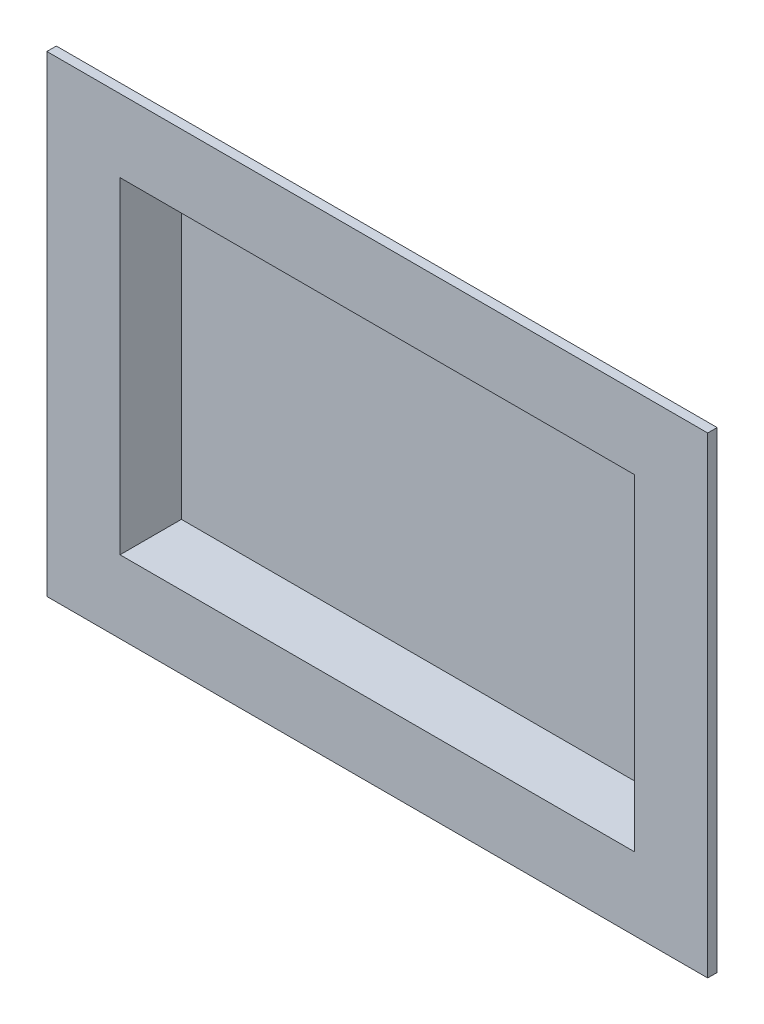
SolidWorks part; units mm, degrees
material "6063-O"
ref_plane "Front Plane" through (0, 0, 0) normal (0, 0, 1) x (1, 0, 0)
ref_plane "Top Plane" through (0, 0, 0) normal (0, 1, 0) x (1, 0, 0)
ref_plane "Right Plane" through (0, 0, 0) normal (1, 0, 0) x (0, 0, -1)
sketch "Sketch1" plane through (0, 0, 0) normal (0, 0, 1) x (1, 0, 0)
  line L1 (-71.755, -46.482) -> (71.755, -46.482)
  line L2 (-71.755, -46.482) -> (-71.755, 46.482)
  line L3 (-71.755, 46.482) -> (71.755, 46.482)
  line L4 (71.755, -46.482) -> (71.755, 46.482)
  line L5 (-71.755, -46.482) -> (71.755, 46.482) construction
  line L6 (-71.755, 46.482) -> (71.755, -46.482) construction
  point P0 (0, 0)
  dimension "D1" = 143.51
  dimension "D2" = 92.964
extrude "Boss-Extrude1" add sketch "Sketch1" against normal blind 16.51
sketch "Sketch2" plane through (0, 0, 0) normal (0, 0, 1) x (1, 0, 0)
  line L1 (-88.9, -63.5) -> (88.9, -63.5)
  line L2 (-88.9, -63.5) -> (-88.9, 63.5)
  line L3 (-88.9, 63.5) -> (88.9, 63.5)
  line L4 (88.9, -63.5) -> (88.9, 63.5)
  line L5 (-88.9, -63.5) -> (88.9, 63.5) construction
  line L6 (-88.9, 63.5) -> (88.9, -63.5) construction
  point P0 (0, 0)
  dimension "D1" = 177.8
  dimension "D2" = 127
extrude "Boss-Extrude2" add sketch "Sketch2" along normal blind 2.54
shell "Shell1" thickness 2.54 removed face at (0, 0, 2.54)
